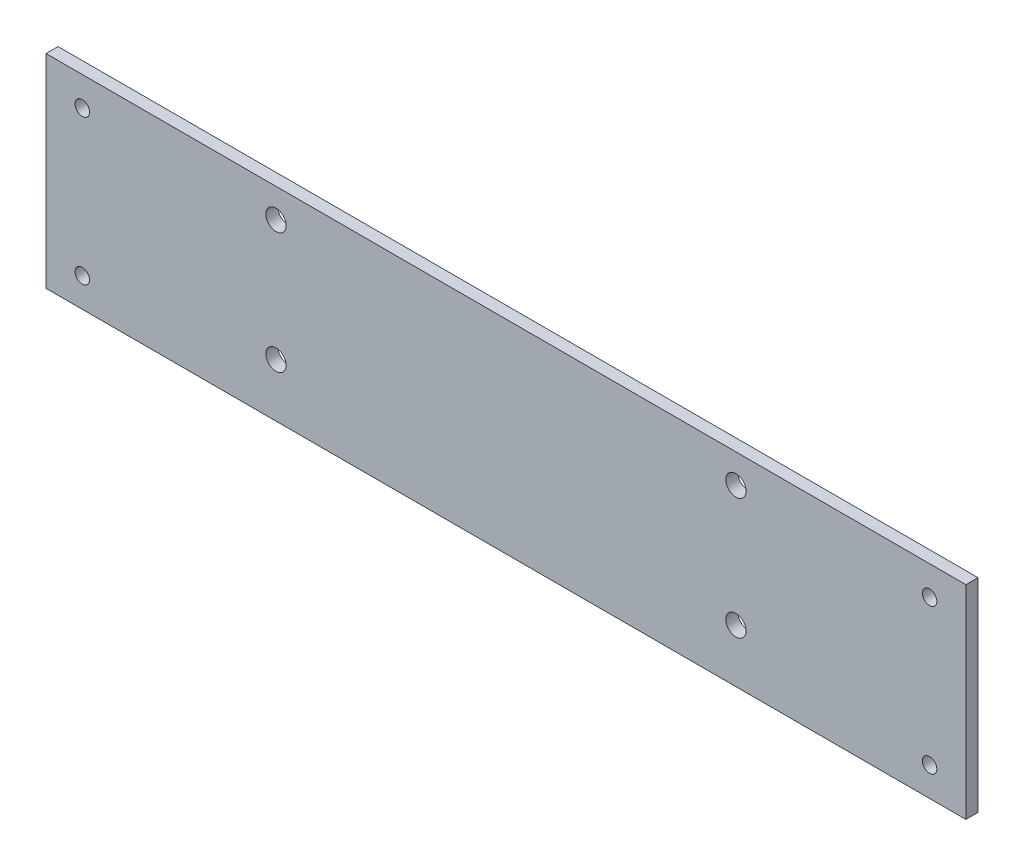
SolidWorks part; units mm, degrees
ref_plane "前视基准面" through (0, 0, 0) normal (0, 0, 1) x (1, 0, 0)
ref_plane "上视基准面" through (0, 0, 0) normal (0, 1, 0) x (1, 0, 0)
ref_plane "右视基准面" through (0, 0, 0) normal (1, 0, 0) x (0, 0, -1)
sketch "Sketch1" plane through (0, 0, 0) normal (0, 0, 1) x (1, 0, 0)
  line L0 (-129.2259, 81.6042) -> (-129.2259, -63.3958) construction
  line L1 (-129.2259, 44.0673) -> (60.7741, 44.0673)
  line L2 (-129.2259, 44.0673) -> (-129.2259, -5.9327)
  line L3 (-129.2259, -5.9327) -> (60.7741, -5.9327)
  line L4 (60.7741, 44.0673) -> (60.7741, -5.9327)
  line L5 (60.7741, 81.6042) -> (60.7741, -63.3958) construction
  dimension "D2" = 50
  dimension "D3" = 0
  dimension "D4" = 0
extrude "Boss-Extrude1" add sketch "Sketch1" along normal blind 2.5
sketch "Sketch2" plane through (0, 0, 2.5) normal (0, 0, 1) x (1, 0, 0)
  line L0 (-129.2259, 44.0673) -> (-129.2259, -5.9327) construction
  line L1 (60.7741, -5.9327) -> (60.7741, 44.0673) construction
  line L2 (60.7741, 44.0673) -> (-129.2259, 44.0673) construction
  line L3 (-129.2259, -5.9327) -> (60.7741, -5.9327) construction
  circle A0 centre (-121.7259, 34.0673) radius 1.5
  circle A1 centre (-121.7259, 4.0673) radius 1.5
  circle A2 centre (53.2741, 34.0673) radius 1.5
  circle A3 centre (53.2741, 4.0673) radius 1.5
  dimension "D1" = 3
  dimension "D2" = 3
  dimension "D3" = 3
  dimension "D4" = 3
  dimension "D5" = 7.5
  dimension "D6" = 7.5
  dimension "D8" = 7.5
  dimension "D9" = 10
  dimension "D10" = 10
  dimension "D11" = 10
  dimension "D12" = 10
  dimension "D7" = 7.5
extrude "Cut-Extrude1" cut sketch "Sketch2" against normal through all
sketch "Sketch3" plane through (0, 0, 2.5) normal (0, 0, 1) x (1, 0, 0)
  line L0 (60.7741, 44.0673) -> (-129.2259, 44.0673) construction
  line L1 (-129.2259, 44.0673) -> (-129.2259, -5.9327) construction
  circle A0 centre (-81.7259, 34.0673) radius 2.1
  circle A1 centre (13.2741, 34.0673) radius 2.1
  circle A2 centre (13.2741, 9.0673) radius 2.1
  circle A3 centre (-81.7259, 9.0673) radius 2.1
  dimension "D1" = 4.2
  dimension "D2" = 25
  dimension "D3" = 95
  dimension "D4" = 95
  dimension "D5" = 25
  dimension "D6" = 4.2
  dimension "D7" = 4.2
  dimension "D8" = 4.2
  dimension "D9" = 10
  dimension "D10" = 47.5
  dimension "D11" = 47.5
extrude "Cut-Extrude2" cut sketch "Sketch3" against normal through all
sketch "草图2" plane through (0, 0, 2.5) normal (0, 0, 1) x (1, 0, 0)
  line L0 (-129.2259, 44.0673) -> (-129.2259, -5.9327) construction
  line L1 (-129.2259, 40.0673) -> (60.7741, 40.0673)
  line L2 (-129.2259, 40.0673) -> (-129.2259, -1.9327)
  line L3 (-129.2259, -1.9327) -> (60.7741, -1.9327)
  line L4 (60.7741, 40.0673) -> (60.7741, -1.9327)
  line L5 (60.7741, -5.9327) -> (60.7741, 44.0673) construction
  line L6 (60.7741, 44.0673) -> (-129.2259, 44.0673) construction
  line L7 (-132.726, 50.2016) -> (67.229, 50.2016)
  line L8 (-132.726, 50.2016) -> (-132.726, -10.5946)
  line L9 (-132.726, -10.5946) -> (67.229, -10.5946)
  line L10 (67.229, 50.2016) -> (67.229, -10.5946)
  line L11 (-129.2259, -5.9327) -> (60.7741, -5.9327) construction
  dimension "D1" = 4
  dimension "D2" = 4
extrude "切除-拉伸1" cut sketch "草图2" against normal blind 10
